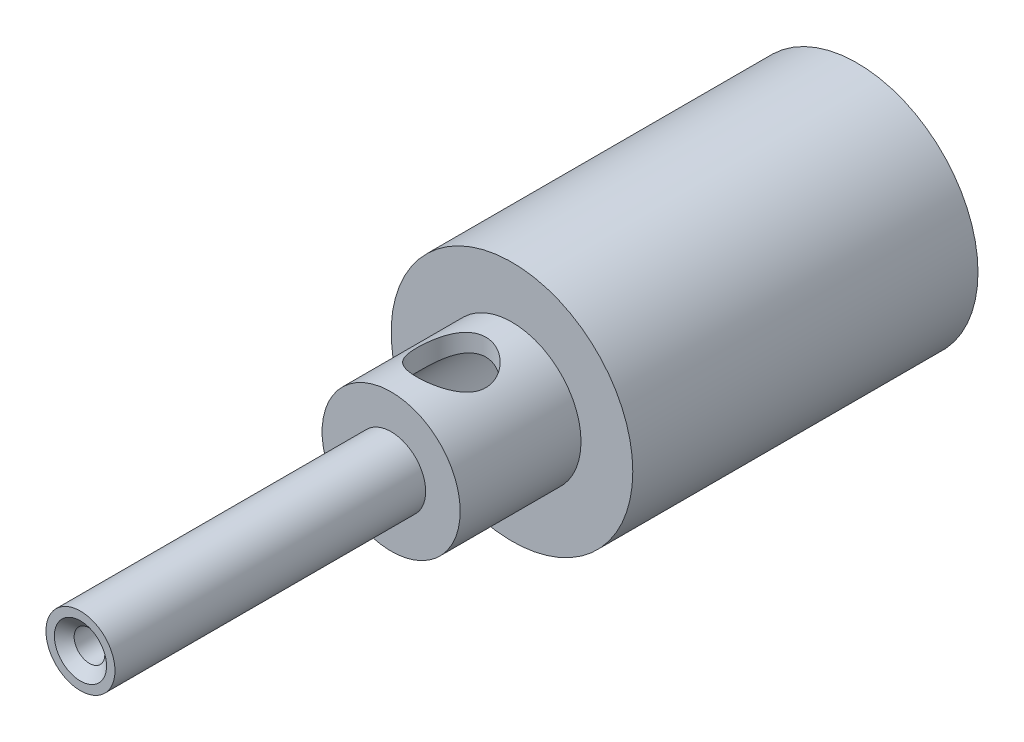
SolidWorks part; units mm, degrees
material "AISI 1020"
ref_plane "Front" through (0, 0, 0) normal (0, 0, 1) x (1, 0, 0)
ref_plane "Top" through (0, 0, 0) normal (0, 1, 0) x (1, 0, 0)
ref_plane "Right" through (0, 0, 0) normal (1, 0, 0) x (0, 0, -1)
sketch "Sketch1" plane through (0, 0, 0) normal (0, 0, 1) x (1, 0, 0)
  circle A0 centre (0, 0) radius 7
extrude "Boss-Extrude1" add sketch "Sketch1" along normal blind 20
sketch "Sketch2" plane through (0, 0, 20) normal (0, 0, 1) x (1, 0, 0)
  circle A0 centre (0, 0) radius 4
extrude "Boss-Extrude2" add sketch "Sketch2" along normal blind 7
sketch "Sketch3" plane through (0, 0, 27) normal (0, 0, 1) x (1, 0, 0)
  circle A0 centre (0, 0) radius 2
extrude "Boss-Extrude3" add sketch "Sketch3" along normal blind 18
sketch "Sketch5" plane through (0, 0, 45) normal (0, 0, 1) x (1, 0, 0)
  circle A0 centre (0, 0) radius 1
sketch "Sketch6" plane through (0, 0, 0) normal (0, 1, 0) x (1, 0, 0)
  circle A0 centre (0, -23.5116) radius 2
extrude "Cut-Extrude3" cut sketch "Sketch6" against normal blind 32 and the other way blind 32
hole_wizard "CSK for #0 Flat Head Machine Screw (100)1" positions "Sketch8" profile "Sketch9" countersink size "#0" standard "ANSI Inch" end condition up to next
sketch "Sketch8" plane through (0, 0, 45) normal (0, 0, 1) x (1, 0, 0)
  point P0 (0, 0)
sketch "Sketch9" plane through (0, 0, 45) normal (1, 0, 0) x (0, -1, 0)
  line L0 (0, 0) -> (0, 19.4884)
  line L1 (0, 19.4884) -> (0.889, 19.4884)
  line L2 (0.889, 19.4884) -> (0.889, 0.5222)
  line L3 (0.889, 0.5222) -> (1.5113, 0)
  line L5 (1.5113, 0) -> (0, 0)
  line L6 (-0.889, 0.5222) -> (-1.5113, 0) construction
  line L11 (0, -6.35) -> (0, 107.95) construction
  dimension "Thru Hole Dia." = 1.778
  dimension "Thru Hole Depth" = 19.4884
  dimension "Near C'Sink Dia." = 3.0226
  dimension "Near C'Sink Angle" = 100
sketch "Sketch12" plane through (0, 0, 0) normal (0, 0, -1) x (-1, 0, 0)
  circle A0 centre (0, 0) radius 4
extrude "Boss-Extrude4" add sketch "Sketch12" along normal blind 1
sketch "Sketch4" plane through (0, 0, 0) normal (0, 0, -1) x (-1, 0, 0)
  circle A0 centre (0, 0) radius 3
extrude "Cut-Extrude5" cut sketch "Sketch4" against normal blind 26.8849 and the other way blind 8 contours A0
